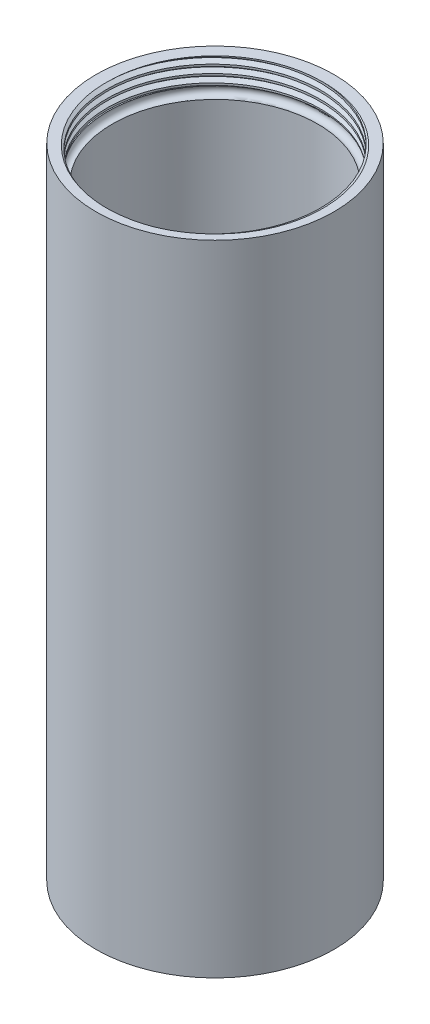
SolidWorks part; units mm, degrees
other "Marcação1"
sketch "Esboço95" plane through (-36.5, 0, -36.5) normal (-0.6691, 0.7292, -0.1437) x (0.7423, 0.6461, -0.1775)
material "1.0401 (C15)"
ref_plane "Plano frontal" through (0, 0, 0) normal (0, 0, 1) x (1, 0, 0)
ref_plane "Plano superior" through (0, 0, 0) normal (0, 1, 0) x (1, 0, 0)
ref_plane "Plano direito" through (0, 0, 0) normal (1, 0, 0) x (0, 0, -1)
sketch "Esboço1" plane through (0, 0, 0) normal (0, 1, 0) x (1, 0, 0)
  circle A0 centre (0, 0) radius 31.5
  circle A1 centre (0, 0) radius 36.5
  dimension "D1" = 63
  dimension "D3" = 5
extrude "cilíndro" add sketch "Esboço1" against normal blind 196
ref_plane "plano-grelha" through (0, -164, 0) normal (0, -1, 0) x (-1, 0, 0)
sketch "Esboço256" plane through (0, -164, 0) normal (0, -1, 0) x (-1, 0, 0)
  circle A0 centre (0, 0) radius 32.8
  dimension "D1" = 65.6
extrude "grelha" cut sketch "Esboço256" along normal blind 7
ref_plane "plano-anel-tubeira" through (0, -172.27, 0) normal (0, -1, 0) x (-1, 0, 0)
sketch "Esboço10" plane through (0, -196, 0) normal (0, -1, 0) x (1, 0, 0)
  circle A0 centre (0, 0) radius 32.8
  dimension "D1" = 65.6
extrude "tubeira" cut sketch "Esboço10" against normal blind 23.73
thread "rosca-tubeira" pitch 2.5 method cut trim with start face yes trim with end face yes profile "Perfil da rosca13" start angle 0, offset 2.5, length 0, pitch 2.5, diameter 65.6
ref_plane "Plano19" through (32.8, -198.5, 0) normal (0, 0, 1) x (1, 0, 0)
sketch "Perfil da rosca13" plane through (32.8, -198.5, 0) normal (0, 0, 1) x (1, 0, 0)
  line L0 (0, 0) -> (0, 2.5) construction
  line L1 (0, 0) -> (1.3532, 0.7812)
  line L2 (1.3532, 0.7812) -> (1.3532, 1.0937)
  line L3 (1.3532, 1.0937) -> (0, 1.875)
  line L4 (1.3532, 0.9375) -> (0, 0.9375) construction
  line L11 (0, 0) -> (0, 1.875)
  point P2 (0, 0)
  dimension "Pitch" = 2.5
  dimension "Profile_Angle" = 60
  dimension "Profile_Land" = 0.3125
  dimension "Profile_Height" = 1.3532
sketch "Esboço191" plane through (0, -172.27, 0) normal (0, -1, 0) x (-1, 0, 0)
  circle A0 centre (0, 0) radius 32.1
  dimension "D1" = 64.2
sweep "anel-tubeira" cut path "Esboço191" circular profile diameter 3 parameters "D3"=3
sketch "Esboço2" plane through (0, 0, 0) normal (0, 1, 0) x (1, 0, 0)
  circle A0 centre (0, 0) radius 32.8
  dimension "D1" = 65.6
extrude "suporte" cut sketch "Esboço2" along direction (0, 1, 0) on the side against the normal blind 8 contours A0
thread "rosca-suporte" pitch 2.5 method cut trim with start face yes trim with end face yes profile "Perfil da rosca14" start angle 0, offset 2.5, length 0, pitch 2.5, diameter 65.6
ref_plane "Plano21" through (-32.8, 2.5, 0) normal (0, 0, 1) x (-1, 0, 0)
sketch "Perfil da rosca14" plane through (-32.8, 2.5, 0) normal (0, 0, 1) x (-1, 0, 0)
  line L0 (0, 0) -> (0, 2.5) construction
  line L1 (0, 0) -> (1.3532, 0.7812)
  line L2 (1.3532, 0.7812) -> (1.3532, 1.0937)
  line L3 (1.3532, 1.0937) -> (0, 1.875)
  line L4 (1.3532, 0.9375) -> (0, 0.9375) construction
  line L11 (0, 0) -> (0, 1.875)
  point P2 (0, 0)
  dimension "Pitch" = 2.5
  dimension "Profile_Angle" = 60
  dimension "Profile_Land" = 0.3125
  dimension "Profile_Height" = 1.3532
ref_plane "plano-anel-suporte" through (0, -9.27, 0) normal (0, 1, 0) x (1, 0, 0)
sketch "Esboço187" plane through (0, -9.27, 0) normal (0, 1, 0) x (1, 0, 0)
  circle A0 centre (0, 0) radius 32.1
  dimension "D1" = 64.2
sweep "anel-suporte" cut path "Esboço187" circular profile diameter 3 parameters "D3"=3
